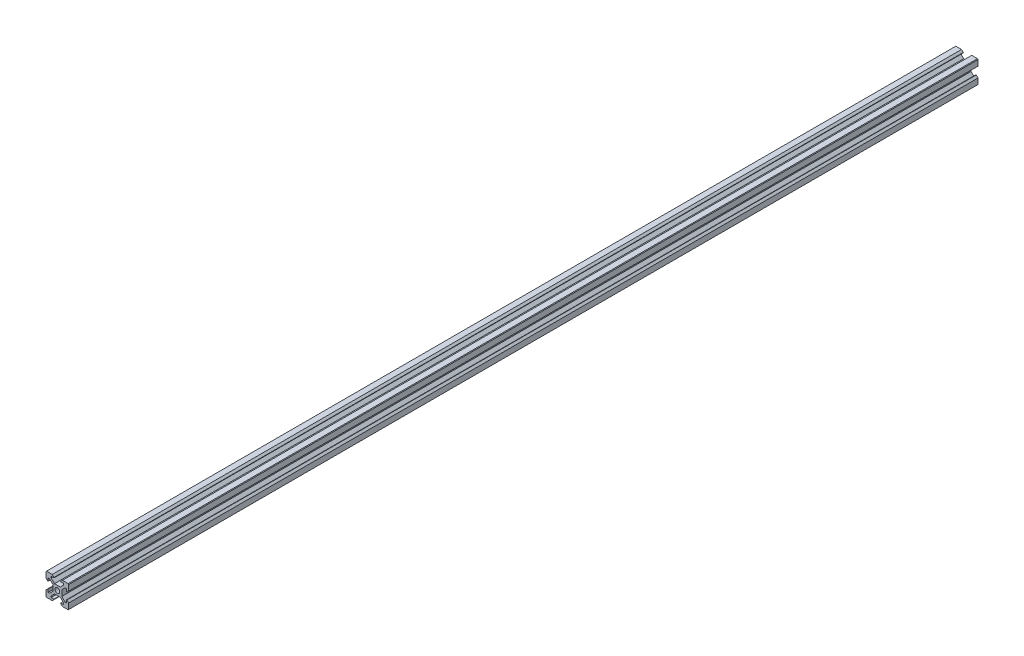
SolidWorks part; units mm, degrees
ref_plane "Front Plane" through (0, 0, 0) normal (0, 0, 1) x (1, 0, 0)
ref_plane "Top Plane" through (0, 0, 0) normal (0, 1, 0) x (1, 0, 0)
ref_plane "Right Plane" through (0, 0, 0) normal (1, 0, 0) x (0, 0, -1)
sketch "Sketch1" plane through (0, 0, 0) normal (0, 0, 1) x (1, 0, 0)
  line L0 (15.6876, 55.3211) -> (115.0437, 55.3211) construction
  line L1 (5.5, 6.8294) -> (2.5706, 3.9)
  line L2 (0, 3.9) -> (0, 2.1)
  line L3 (10, 10) -> (1.4849, 1.4849)
  line L4 (10, 10) -> (4.5, 10)
  line L5 (1.4849, 1.4849) -> (3.9, 3.9) construction
  line L6 (10, -10) -> (-10, 10) construction
  line L7 (10, 10) -> (1.4849, 1.4849) construction
  line L8 (0, 0) -> (-10, -10) construction
  line L10 (0, 3.9) -> (2.5706, 3.9)
  line L12 (-3.9, -3.9) -> (0, 0) construction
  line L13 (-3.9, 3.9) -> (3.9, -3.9) construction
  line L14 (5.5, 6.8294) -> (5.5, 8.12)
  line L15 (5.5, 8.12) -> (2.62, 8.12)
  line L16 (2.62, 8.12) -> (4.5, 10)
  line L17 (0, 2.1) -> (0, 16.7618) construction
  arc A0 (1.4849, 1.4849) -> (0, 2.1) centre (0, 0) ccw
  point P2 (0, 0)
  point P7 (0, 0)
  dimension "D3" = 45
  dimension "D4" = 6.1
  dimension "D8" = 4.2
  dimension "D1" = 20
  dimension "D2" = 11
  dimension "D5" = 1.88
  dimension "D6" = 9
  dimension "D7" = 0.94
  dimension "D9" = 3.9
extrude "Boss-Extrude1" add sketch "Sketch1" along normal blind 800
chamfer "Chamfer2" distance 0.5 angle 45 1 edges at (2.62, 8.12, 400) first distance on face at (3.56, 9.06, 400)
mirror "Mirror1" about plane through (10, 10, 800) normal (-0.7071, 0.7071, 0) of bodies 102
chamfer "Chamfer1" distance 0.5 angle 45 1 edges at (10, 10, 400)
mirror "Mirror4" about plane through (0, 3.9, 800) normal (1, 0, 0) of bodies 103 104
mirror "Mirror5" about plane through (-3.9, 0, 800) normal (0, 1, 0) of bodies 105
